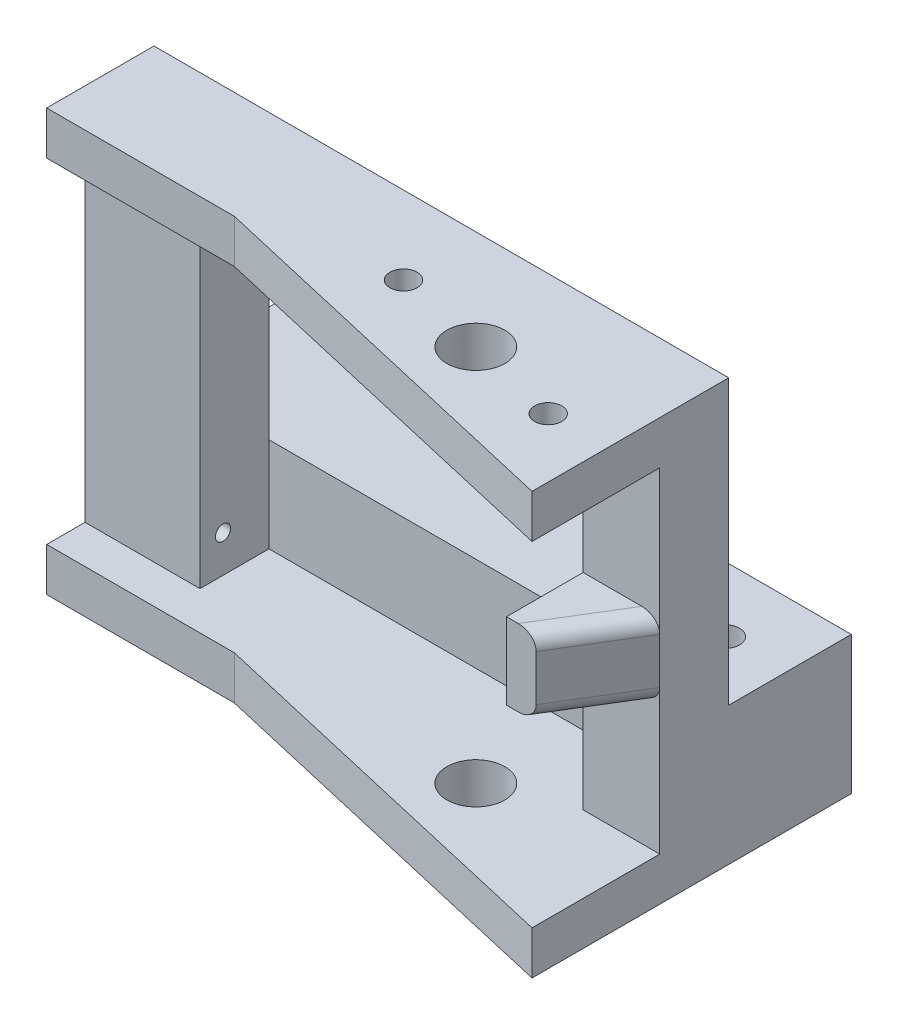
SolidWorks part; units mm, degrees
ref_plane "Front Plane" through (0, 0, 0) normal (0, 0, 1) x (1, 0, 0)
ref_plane "Top Plane" through (0, 0, 0) normal (0, 1, 0) x (1, 0, 0)
ref_plane "Right Plane" through (0, 0, 0) normal (1, 0, 0) x (0, 0, -1)
sketch "Sketch1" plane through (0, 0, 0) normal (0, 0, 1) x (1, 0, 0)
  line L1 (57.15, -34.925) -> (-57.15, -34.925)
  line L2 (57.15, -34.925) -> (57.15, 34.925)
  line L3 (57.15, 34.925) -> (-57.15, 34.925)
  line L4 (-57.15, -34.925) -> (-57.15, 34.925)
  line L5 (57.15, -34.925) -> (-57.15, 34.925) construction
  line L6 (57.15, 34.925) -> (-57.15, -34.925) construction
  point P0 (0, 0)
  dimension "D1" = 69.85
  dimension "D2" = 114.3
extrude "Boss-Extrude1" add sketch "Sketch1" along normal blind 57.15
sketch "Sketch2" plane through (0, 0, 57.15) normal (0, 0, 1) x (1, 0, 0)
  line L0 (-57.15, 34.925) -> (-57.15, -34.925) construction
  line L1 (57.15, -27.725) -> (-57.15, -27.725)
  line L2 (57.15, -27.725) -> (57.15, 27.725)
  line L3 (57.15, 27.725) -> (-57.15, 27.725)
  line L4 (-57.15, -27.725) -> (-57.15, 27.725)
  line L5 (57.15, -27.725) -> (-57.15, 27.725) construction
  line L6 (57.15, 27.725) -> (-57.15, -27.725) construction
  line L7 (57.15, 34.925) -> (-57.15, 34.925) construction
  point P0 (0, 0)
  dimension "D1" = 7.2
extrude "Cut-Extrude2" cut sketch "Sketch2" against normal blind 25.4
sketch "Sketch3" plane through (0, 0, 0) normal (0, 0, -1) x (-1, 0, 0)
  line L0 (-57.15, -34.925) -> (-57.15, 34.925) construction
  line L1 (57.15, 34.925) -> (-57.15, 34.925)
  line L2 (57.15, 34.925) -> (57.15, -12.065)
  line L3 (57.15, -12.065) -> (-57.15, -12.065)
  line L4 (-57.15, 34.925) -> (-57.15, -12.065)
  dimension "D1" = 46.99
extrude "Cut-Extrude3" cut sketch "Sketch3" against normal blind 20.32
sketch "Sketch5" plane through (0, -34.925, 0) normal (0, -1, 0) x (1, 0, 0)
  line L0 (-3.81, 10.79) -> (46.99, 10.79) construction
  line L1 (57.15, 20.32) -> (-57.15, 20.32) construction
  line L2 (57.15, 57.15) -> (57.15, 0) construction
  circle A0 centre (-3.81, 10.79) radius 2.415
  circle A1 centre (46.99, 10.79) radius 2.415
  dimension "D3" = 4.83
  dimension "D4" = 10.16
  dimension "D1" = 9.53
  dimension "D2" = 50.8
extrude "Cut-Extrude4" cut sketch "Sketch5" against normal blind 25.4
sketch "Sketch6" plane through (0, 0, 20.32) normal (0, 0, -1) x (-1, 0, 0)
  line L0 (-49.405, -12.065) -> (6.225, -12.065) construction
  line L1 (-49.405, -12.065) -> (-49.405, -34.925) construction
  line L2 (6.225, -34.925) -> (6.225, -12.065) construction
  line L3 (-57.15, -12.065) -> (57.15, -12.065) construction
  circle A1 centre (-5.08, -1.524) radius 2.2225
  dimension "D3" = 4.445
extrude "Cut-Extrude5" cut sketch "Sketch6" against normal blind 5.08
sketch "Sketch7" plane through (0, -34.925, 0) normal (0, -1, 0) x (1, 0, 0)
  line L0 (57.15, 57.15) -> (57.15, 0) construction
  line L2 (-57.15, 31.75) -> (57.15, 31.75) construction
  circle A0 centre (31.75, 36.83) radius 4.8
  dimension "D1" = 9.6
  dimension "D2" = 25.4
  dimension "D3" = 5.08
extrude "Cut-Extrude6" cut sketch "Sketch7" against normal up to surface (69.85 mm away) up to face at (0, 34.925, 38.735)
sketch "Sketch8" plane through (0, 34.925, 0) normal (0, 1, 0) x (1, 0, 0)
  line L0 (16.1601, -33.2308) -> (47.3399, -40.4292) construction
  line L1 (57.15, -31.75) -> (-57.15, -31.75) construction
  circle A0 centre (31.75, -36.83) radius 16 construction
  circle A1 centre (16.1601, -33.2308) radius 2.25
  circle A2 centre (47.3399, -40.4292) radius 2.25
  dimension "D1" = 32
  dimension "D2" = 4.5
  dimension "D3" = 13
sketch "Sketch9" plane through (0, 0, 31.75) normal (0, 0, 1) x (1, 0, 0)
  line L0 (57.15, 34.925) -> (-57.15, 34.925) construction
  line L5 (57.15, 27.725) -> (-57.15, 27.725) construction
  line L6 (-19.05, 27.725) -> (44.45, 27.725)
  line L7 (-19.05, 27.725) -> (-19.05, -27.725)
  line L8 (-19.05, -27.725) -> (44.45, -27.725)
  line L9 (44.45, 27.725) -> (44.45, -27.725)
  line L10 (-57.15, -27.725) -> (57.15, -27.725) construction
  line L11 (-57.15, 27.725) -> (-57.15, -27.725) construction
  line L12 (57.15, -27.725) -> (57.15, 27.725) construction
  line L13 (-57.15, -34.925) -> (-38.1, -34.925)
  line L14 (-57.15, -34.925) -> (-57.15, 34.925)
  line L15 (-57.15, 34.925) -> (-38.1, 34.925)
  line L16 (-38.1, -34.925) -> (-38.1, 34.925)
  line L17 (-57.15, -34.925) -> (-38.1, 34.925) construction
  line L18 (-57.15, 34.925) -> (-38.1, -34.925) construction
  line L19 (-57.15, -34.925) -> (57.15, -34.925) construction
  point P5 (-47.625, 0)
  dimension "D1" = 12.7
  dimension "25in" = 38.1
  dimension "D2" = 19.05
extrude "Cut-Extrude7" cut sketch "Sketch9" against normal through all both and the other way through all
extrude "Cut-Extrude8" cut sketch "Sketch8" against normal up to next
sketch "Sketch10" [suppressed] plane through (0, 0, 29.21) normal (0, 0, 1) x (1, 0, 0)
  line L1 (-30.607, -1.778) -> (-30.607, -6.604) construction
  circle A0 centre (-33.2489, -4.191) radius 2.286
  point P5 (-30.607, -4.191)
  dimension "D1" = 4.572
sketch "Sketch11" [suppressed] plane through (0, 0, 21.59) normal (0, 0, -1) x (-1, 0, 0)
  circle A0 centre (33.2489, -4.191) radius 2.286
  dimension "D1" = 4.572
extrude "Cut-Extrude9" [suppressed] cut sketch "Sketch11" against normal blind 3.81
sketch "Sketch12" plane through (-19.05, 0, 0) normal (1, 0, 0) x (0, 0, -1)
  line L0 (-31.75, -27.725) -> (-31.75, 27.725) construction
  line L1 (-27.94, -21.59) -> (-27.94, 21.59) construction
  line L2 (-20.32, 27.725) -> (-20.32, -12.065) construction
  circle A0 centre (-27.94, -21.59) radius 1.25
  circle A1 centre (-27.94, 21.59) radius 1.25
  point P0 (-31.75, 0)
  point P8 (-27.94, 0)
  dimension "D1" = 2.5
  dimension "D2" = 7.62
  dimension "D3" = 43.18
extrude "Cut-Extrude10" cut sketch "Sketch12" against normal up to surface (19.05 mm away) up to face at (-38.1, -2.413, 33.274)
sketch "Sketch13" plane through (0, 34.925, 0) normal (0, 1, 0) x (1, 0, 0)
  line L0 (-38.1, -38.1077) -> (-6.9983, -38.1077)
  line L1 (-6.9983, -38.1077) -> (75.4829, -57.15)
  line L2 (57.15, -57.15) -> (-38.1, -57.15) construction
  line L3 (47.3399, -40.4292) -> (16.1601, -33.2308) construction
  line L4 (-38.1, -38.1077) -> (-38.1, -57.15)
  line L5 (-38.1, -57.15) -> (75.4829, -57.15)
  line L6 (-38.1, -20.32) -> (-38.1, -57.15) construction
  point P2 (57.8965, -57.15)
  point P12 (-6.9983, -38.1077)
  point P14 (0, 0)
extrude "Cut-Extrude12" cut sketch "Sketch13" against normal through all
sketch "Sketch14" plane through (44.45, 0, 0) normal (-1, 0, 0) x (0, 0, 1)
  line L0 (0, -27.725) -> (31.75, -27.725) construction
  line L1 (20.32, -12.065) -> (0, -12.065)
  line L2 (20.32, -12.065) -> (20.32, -27.725)
  line L3 (20.32, -27.725) -> (0, -27.725)
  line L4 (0, -12.065) -> (0, -27.725)
extrude "Boss-Extrude2" add sketch "Sketch14" along normal up to next
sketch "Sketch15" plane through (0, 0, 20.32) normal (0, 0, -1) x (-1, 0, 0)
  line L0 (22.6367, 0.762) -> (22.6367, -4.064) construction
  line L2 (17.6714, 0.8658) -> (32.5377, 0.555) construction
  line L3 (22.6367, 0.762) -> (22.6367, -4.064) construction
  line L4 (27.4632, -4.064) -> (17.5572, -4.064) construction
  line L5 (21.717, -0.889) -> (21.717, 3.937) construction
  circle A0 centre (23.967, -1.651) radius 2.25
  point P4 (22.6367, -1.651)
  dimension "D1" = 4.5
extrude "Cut-Extrude13" cut sketch "Sketch15" against normal blind 5.08
sketch "Sketch16" plane through (0, 0, 31.75) normal (0, 0, 1) x (1, 0, 0)
  line L0 (44.45, -27.725) -> (44.45, 27.725) construction
  line L1 (57.15, -6.35) -> (44.45, -6.35)
  line L2 (57.15, -6.35) -> (57.15, 6.35)
  line L3 (57.15, 6.35) -> (44.45, 6.35)
  line L4 (44.45, -6.35) -> (44.45, 6.35)
  line L5 (57.15, -6.35) -> (44.45, 6.35) construction
  line L6 (57.15, 6.35) -> (44.45, -6.35) construction
  line L7 (57.15, 6.35) -> (57.15, -6.35) construction
  line L9 (57.15, -27.725) -> (57.15, 27.725) construction
  point P0 (50.8, 0)
  point P7 (57.15, 0)
  dimension "D1" = 12.7
extrude "Boss-Extrude3" add sketch "Sketch16" along normal blind 12.7
sketch "Sketch17" plane through (0, 6.35, 0) normal (0, 1, 0) x (1, 0, 0)
  line L0 (49.375, -44.45) -> (57.15, -31.75)
  line L1 (57.15, -44.45) -> (57.15, -31.75) construction
  line L2 (57.15, -31.75) -> (44.45, -31.75) construction
  line L3 (57.15, -31.75) -> (57.15, -44.45)
  line L4 (57.15, -44.45) -> (49.375, -44.45)
  line L5 (57.15, -44.45) -> (44.45, -44.45) construction
extrude "Cut-Extrude14" cut sketch "Sketch17" against normal blind 12.7
fillet "Fillet4" radius 2.54 2 edges at (53.2625, -6.35, 38.1) (53.2625, 6.35, 38.1)
